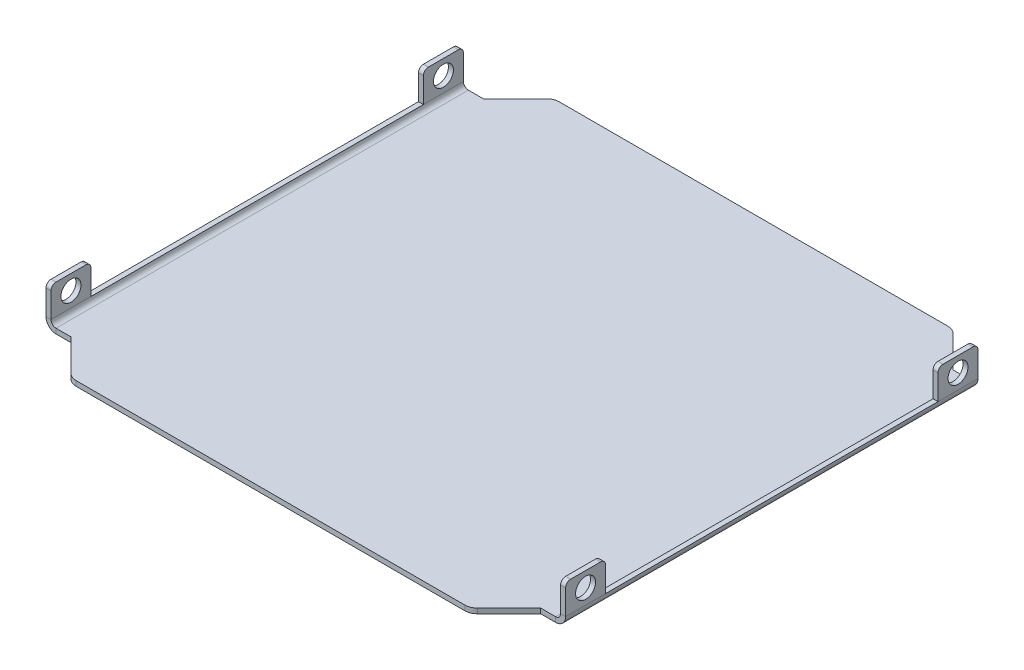
SolidWorks part; units mm, degrees
note: The reader was unsure of these and kept them because the rebuilt part matched: flange length of "Edge-Flange1".
material "6061-T6 (SS)"
ref_plane "Front Plane" through (0, 0, 0) normal (0, 0, 1) x (1, 0, 0)
ref_plane "Top Plane" through (0, 0, 0) normal (0, 1, 0) x (1, 0, 0)
ref_plane "Right Plane" through (0, 0, 0) normal (1, 0, 0) x (0, 0, -1)
sketch "Sketch1" plane through (0, 0, 0) normal (0, 1, 0) x (1, 0, 0)
  line L2 (0, 0) -> (0, 82.6)
  line L4 (104.072, 0) -> (104.072, 82.6)
  line L33 (104.072, 82.6) -> (99.072, 82.6)
  line L37 (5, 82.6) -> (0, 82.6)
  line L38 (5, 82.6) -> (12.0711, 89.6711)
  line L40 (92.0009, 89.6711) -> (99.072, 82.6)
  line L41 (0, 41.3) -> (104.072, 41.3) construction
  line L42 (92.0009, -7.0711) -> (99.072, 0)
  line L43 (12.0711, -7.0711) -> (92.0009, -7.0711)
  line L44 (5, 0) -> (12.0711, -7.0711)
  line L45 (5, 0) -> (0, 0)
  line L46 (104.072, 0) -> (99.072, 0)
  line L61 (92.0009, 89.6711) -> (12.0711, 89.6711)
  dimension "D1" = 82.6
  dimension "D2" = 104.072
  dimension "D3" = 5
  dimension "D4" = 79.9299
  dimension "D5" = 135
  dimension "D6" = 135
  dimension "D7" = 10
base flange "Base-Flange2" sketch "Sketch1" thickness 1 reverse thickness direction no parameters "D1"=1
edge flange "Edge-Flange1" sketch "Sketch14" flange profiles "Sketch14", "Sketch15" flange angle 90 flange length 8 flange position material inside bend radius 1 thickness 1 relief rectangular parameters "D6"=10, "D8"=1
sketch "Sketch14" plane through (104.072, 0, 0) normal (1, 0, 0) x (0, 0, -1)
  line L0 (0, 0) -> (82.6, 0) construction
  line L1 (0, 0) -> (82.6, 0)
  line L2 (0, 0) -> (0, 7)
  line L3 (0, 7) -> (82.6, 7)
  line L4 (82.6, 7) -> (82.6, 0)
  dimension "D1" = 7
sketch "Sketch15" plane through (0, 0, 0) normal (-1, 0, 0) x (0, 0, 1)
  line L0 (-82.6, 0) -> (0, 0) construction
  line L1 (-82.6, 0) -> (0, 0)
  line L2 (-82.6, 0) -> (-82.6, 7)
  line L3 (-82.6, 7) -> (0, 7)
  line L4 (0, 7) -> (0, 0)
  dimension "D1" = 7
bend "EdgeBend1" bend radius 1 bend angle 90 parameters "D5"=1
bend "EdgeBend2" bend radius 1 bend angle 90 parameters "D5"=2
sketch "Sketch16" plane through (104.072, 0, 0) normal (1, 0, 0) x (0, 0, -1)
  line L0 (82.6, 1) -> (0, 1) construction
  line L1 (8, 8) -> (74.6, 8)
  line L2 (8, 8) -> (8, 1)
  line L3 (8, 1) -> (74.6, 1)
  line L4 (74.6, 8) -> (74.6, 1)
  line L5 (0, 7) -> (0, 1) construction
  line L6 (82.6, 1) -> (82.6, 7) construction
  line L7 (82.6, 7) -> (0, 7) construction
  dimension "D1" = 8
  dimension "D2" = 8
  dimension "D3" = 1
extrude "Cut-Extrude1" cut sketch "Sketch16" against normal through all normal cut yes
fillet "Fillet1" radius 1 8 edges at (0.5, 7, -8) (0.5, 7, 0) (0.5, 7, -74.6) (0.5, 7, -82.6) (103.572, 7, -74.6) (103.572, 7, -82.6) (103.572, 7, 0) (103.572, 7, -8)
sketch "Sketch17" plane through (104.072, 0, 0) normal (1, 0, 0) x (0, 0, -1)
  line L0 (-7.0711, 0) -> (0, 0) construction
  line L1 (0, 6) -> (0, 1) construction
  line L2 (82.6, 0) -> (89.6711, 0) construction
  line L3 (82.6, 1) -> (82.6, 6) construction
  circle A0 centre (4, 4) radius 2
  circle A1 centre (78.6, 4) radius 2
  dimension "D1" = 4
  dimension "D4" = 4
  dimension "D2" = 4
  dimension "D3" = 4
  dimension "D5" = 4
  dimension "D6" = 4
extrude "Cut-Extrude2" cut sketch "Sketch17" against normal through all normal cut yes
fillet "Fillet2" radius 2.5 4 edges at (12.0711, -0.5, -89.6711) (92.0009, -0.5, -89.6711) (92.0009, -0.5, 7.0711) (12.0711, -0.5, 7.0711)
sketch "Bend-Lines3" [suppressed] plane through (0, 0, 0) normal (0, 1, 0) x (1, 0, 0)
sketch "Bounding-Box3" [suppressed] plane through (0, 0, 0) normal (0, 1, 0) x (1, 0, 0)
sheet metal parameters "Sheet-Metal2" thickness 1 parameters "D1"=1
flat pattern "Flat-Pattern2" [suppressed]
sketch "Bend-Lines4" plane through (0, 0, 0) normal (0, 1, 0) x (1, 0, 0)
sketch3d "Bounding-Box4" [suppressed]
  line L0 (-135.6338, 86.2583, 0) -> (0, 86.2583, 0) construction
  line L1 (-135.6338, 0, 0) -> (0, 0, 0) construction
  line L2 (-135.6338, 86.2583, 0) -> (-135.6338, 0, 0) construction
  line L3 (0, 86.2583, 0) -> (0, 0, 0) construction
sheet metal parameters "Sheet-Metal3" thickness 1 parameters "D1"=1
flat pattern "Flat-Pattern2"
sketch "Bend-Lines4" plane through (0, 0, 0) normal (0, 1, 0) x (1, 0, 0)
sketch3d "Bounding-Box4" [suppressed]
  line L0 (-135.6338, 86.2583, 0) -> (0, 86.2583, 0) construction
  line L1 (-135.6338, 0, 0) -> (0, 0, 0) construction
  line L2 (-135.6338, 86.2583, 0) -> (-135.6338, 0, 0) construction
  line L3 (0, 86.2583, 0) -> (0, 0, 0) construction
bend of the flat pattern "Flatten-<EdgeBend1>1"
bend of the flat pattern "Flatten-<EdgeBend2>1"
sheet metal parameters "Sheet-Metal4" thickness 1 parameters "D1"=1
flat pattern "Flat-Pattern2"
sketch "Bend-Lines4" plane through (0, 0, 0) normal (0, 1, 0) x (1, 0, 0)
sketch3d "Bounding-Box4" [suppressed]
  line L0 (-135.6338, 86.2583, 0) -> (0, 86.2583, 0) construction
  line L1 (-135.6338, 0, 0) -> (0, 0, 0) construction
  line L2 (-135.6338, 86.2583, 0) -> (-135.6338, 0, 0) construction
  line L3 (0, 86.2583, 0) -> (0, 0, 0) construction
bend of the flat pattern "Flatten-<EdgeBend1>1"
bend of the flat pattern "Flatten-<EdgeBend2>1"
sheet metal parameters "Sheet-Metal5" thickness 1 parameters "D1"=1
flat pattern "Flat-Pattern2"
sketch "Bend-Lines4" plane through (0, 0, 0) normal (0, 1, 0) x (1, 0, 0)
sketch3d "Bounding-Box4" [suppressed]
  line L0 (-135.6338, 86.2583, 0) -> (0, 86.2583, 0) construction
  line L1 (-135.6338, 0, 0) -> (0, 0, 0) construction
  line L2 (-135.6338, 86.2583, 0) -> (-135.6338, 0, 0) construction
  line L3 (0, 86.2583, 0) -> (0, 0, 0) construction
bend of the flat pattern "Flatten-<EdgeBend1>1"
bend of the flat pattern "Flatten-<EdgeBend2>1"
